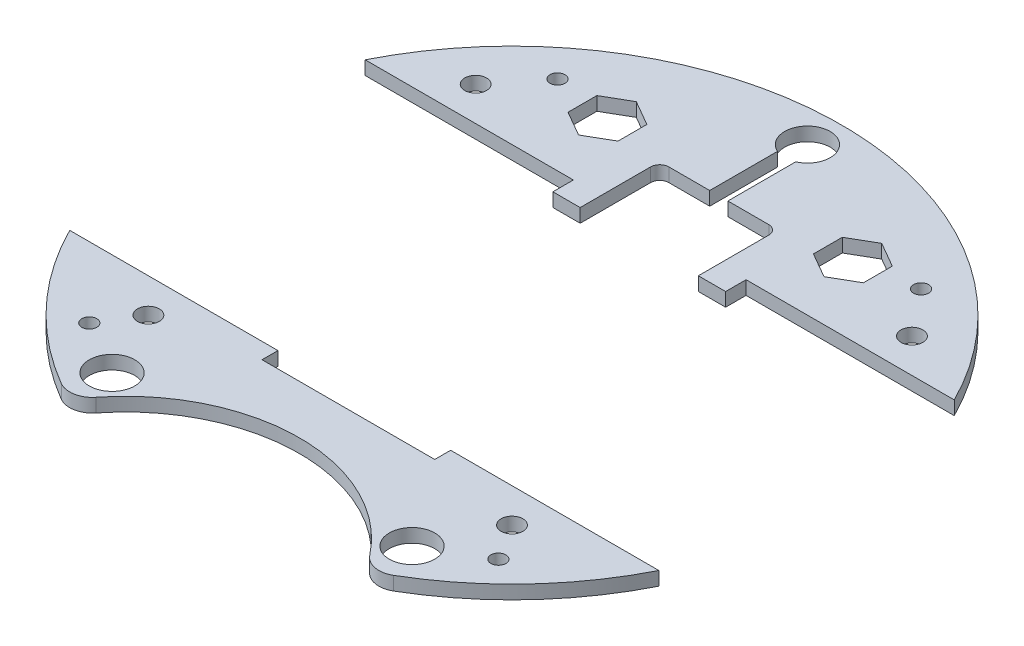
SolidWorks part; units mm, degrees
material "Acrylic (Medium-high impact)"
ref_plane "Front Plane" through (0, 0, 0) normal (0, 0, 1) x (1, 0, 0)
ref_plane "Top Plane" through (0, 0, 0) normal (0, 1, 0) x (1, 0, 0)
ref_plane "Right Plane" through (0, 0, 0) normal (1, 0, 0) x (0, 0, -1)
sketch "Sketch1" plane through (0, 0, 0) normal (0, 1, 0) x (1, 0, 0)
  line L0 (0, -85) -> (-32.4891, -64.8129) construction
  line L1 (0, -85) -> (0, 0) construction
  arc A0 (36.5434, -62.6165) -> (-36.5434, -62.6165) centre (0, 0) ccw
  arc A1 (30.0898, -61.3851) -> (-30.0898, -61.3851) centre (0, -85) ccw
  arc A2 (36.5434, -62.6165) -> (30.0898, -61.3851) centre (34.0231, -58.2982) cw
  arc A3 (-30.0898, -61.3851) -> (-36.5434, -62.6165) centre (-34.0231, -58.2982) cw
  dimension "D1" = 145
  dimension "D2" = 76.5
  dimension "D4" = 5
  dimension "D3" = 85
extrude "Boss-Extrude1" add sketch "Sketch1" along normal blind 3
sketch "solenoid placement" plane through (0, 3, 0) normal (0, 1, 0) x (1, 0, 0)
  line L4 (-19, -36) -> (19, -36)
  line L5 (-19, 28) -> (-19, -36)
  line L6 (19, 28) -> (-19, 28)
  line L7 (19, -36) -> (19, 28)
  line L8 (-19, -36) -> (19, -36)
  line L9 (-19, 28) -> (-19, -36)
  line L10 (19, 28) -> (-19, 28)
  line L11 (19, -36) -> (19, 28)
  dimension "D1" = 0
extrude "Cut-Extrude1" cut sketch "solenoid placement" against normal through all
sketch "Sketch5" plane through (0, 3, 0) normal (0, 1, 0) x (1, 0, 0)
  line L12 (-21.5, 51.1754) -> (-27, 54.3509)
  line L13 (-27, 54.3509) -> (-32.5, 51.1754)
  line L14 (-32.5, 51.1754) -> (-32.5, 44.8246)
  line L15 (-32.5, 44.8246) -> (-27, 41.6491)
  line L16 (-27, 41.6491) -> (-21.5, 44.8246)
  line L17 (-21.5, 44.8246) -> (-21.5, 51.1754)
  line L18 (-21.5, 51.1754) -> (-27, 54.3509)
  line L19 (-27, 54.3509) -> (-32.5, 51.1754)
  line L20 (-32.5, 51.1754) -> (-32.5, 44.8246)
  line L21 (-32.5, 44.8246) -> (-27, 41.6491)
  line L22 (-27, 41.6491) -> (-21.5, 44.8246)
  line L23 (-21.5, 44.8246) -> (-21.5, 51.1754)
  line L24 (21.5, 51.1754) -> (21.5, 44.8246)
  line L25 (21.5, 44.8246) -> (27, 41.6491)
  line L26 (27, 41.6491) -> (32.5, 44.8246)
  line L27 (32.5, 44.8246) -> (32.5, 51.1754)
  line L28 (32.5, 51.1754) -> (27, 54.3509)
  line L29 (27, 54.3509) -> (21.5, 51.1754)
  line L42 (21.5, 51.1754) -> (21.5, 44.8246)
  line L43 (21.5, 44.8246) -> (27, 41.6491)
  line L44 (27, 41.6491) -> (32.5, 44.8246)
  line L45 (32.5, 44.8246) -> (32.5, 51.1754)
  line L46 (32.5, 51.1754) -> (27, 54.3509)
  line L47 (27, 54.3509) -> (21.5, 51.1754)
  dimension "D1" = 0
  dimension "D2" = 0
extrude "Cut-Extrude5" cut sketch "Sketch5" against normal through all
sketch "Sketch6" plane through (0, 3, 0) normal (0, 1, 0) x (1, 0, 0)
  circle A0 centre (48, 40) radius 2.4
  circle A1 centre (40, -40) radius 2.4
  circle A2 centre (40, -40) radius 2.4 construction
  circle A3 centre (-40, -40) radius 2.4
  circle A4 centre (-40, -40) radius 2.4 construction
  circle A5 centre (48, 40) radius 2.4
  circle A6 centre (48, 40) radius 2.4 construction
  circle A7 centre (-48, 40) radius 2.4
  circle A8 centre (-48, 40) radius 2.4 construction
  circle A9 centre (-48, 40) radius 2.4
  circle A10 centre (40, -40) radius 2.4
  circle A11 centre (-40, -40) radius 2.4
  dimension "D5" = 4.8
extrude "Cut-Extrude6" cut sketch "Sketch6" against normal through all
sketch "Sketch3" plane through (0, 3, 0) normal (0, 1, 0) x (1, 0, 0)
  line L0 (-19, 28) -> (-19, 32.5)
  line L1 (72.5, -32.5) -> (-72.5, -32.5)
  line L2 (72.5, -32.5) -> (72.5, 32.5)
  line L3 (72.5, 32.5) -> (19, 32.5)
  line L4 (-72.5, -32.5) -> (-72.5, 32.5)
  line L5 (72.5, -32.5) -> (-72.5, 32.5) construction
  line L6 (72.5, 32.5) -> (-72.5, -32.5) construction
  line L7 (-19, 28) -> (19, 28)
  line L8 (19, 28) -> (19, 32.5)
  line L9 (-19, 32.5) -> (-72.5, 32.5)
  line L10 (-19, 28) -> (-19, -36) construction
  arc A0 (36.5434, -62.6165) -> (-36.5434, -62.6165) centre (0, 0) ccw construction
  point P0 (0, 0)
  dimension "D1" = 65
extrude "Cut-Extrude3" cut sketch "Sketch3" against normal through all
sketch "Sketch7" plane through (0, 3, 0) normal (0, 1, 0) x (1, 0, 0)
  line L8 (13, 28) -> (13, 43.5)
  line L9 (-13, 28) -> (13, 28)
  line L10 (-13, 43.5) -> (-13, 28)
  line L11 (11, 45.5) -> (-11, 45.5)
  line L28 (13, 28) -> (13, 43.5)
  line L29 (-13, 28) -> (13, 28)
  line L30 (-13, 43.5) -> (-13, 28)
  line L31 (11, 45.5) -> (-11, 45.5)
  arc A4 (-11, 45.5) -> (-13, 43.5) centre (-11, 43.5) ccw
  arc A5 (13, 43.5) -> (11, 45.5) centre (11, 43.5) ccw
  arc A14 (-11, 45.5) -> (-13, 43.5) centre (-11, 43.5) ccw
  arc A15 (13, 43.5) -> (11, 45.5) centre (11, 43.5) ccw
  dimension "D1" = 0
extrude "Cut-Extrude7" cut sketch "Sketch7" against normal through all
sketch "Sketch8" plane through (0, 3, 0) normal (0, 1, 0) x (1, 0, 0)
  line L0 (0, 0) -> (0, -21.9152) construction
  circle A1 centre (33, -55) radius 5
  circle A4 centre (-33, -55) radius 5
  dimension "D3" = 10
  dimension "D1" = 33
  dimension "D2" = 55
extrude "Cut-Extrude8" cut sketch "Sketch8" against normal through all
sketch "Sketch9" plane through (0, 3, 0) normal (0, 1, 0) x (1, 0, 0)
  line L0 (0, 0) -> (0, 65) construction
  line L1 (2, 0) -> (2, 60.4174)
  line L2 (-2, 0) -> (-2, 60.4174)
  line L3 (2, 0) -> (2, 65) construction
  line L4 (-2, 0) -> (-2, 65) construction
  arc A0 (2, 60.4174) -> (-2, 60.4174) centre (0, 65) ccw
  arc A1 (2, 0) -> (-2, 0) centre (0, 0) cw
  dimension "D1" = 10
  dimension "D2" = 65
  dimension "D3" = 2
  dimension "D4" = 2
extrude "Cut-Extrude9" cut sketch "Sketch9" against normal through all
sketch "Sketch10" plane through (0, 3, 0) normal (0, 1, 0) x (1, 0, 0)
  line L0 (0, 0) -> (0, -25.927) construction
  circle A0 centre (45, -48) radius 1.65
  circle A1 centre (-45, -48) radius 1.65
  circle A2 centre (40, 50) radius 1.65
  circle A3 centre (-40, 50) radius 1.65
  dimension "D3" = 3.3
  dimension "D1" = 45
  dimension "D2" = 48
  dimension "D4" = 40
  dimension "D5" = 50
extrude "Cut-Extrude10" cut sketch "Sketch10" against normal blind 10
equation "\"smallPulleyTeeth\"= 30"
equation "\"largePulleyTeeth\"= 30"
equation "\"eighthThick\"= 3.0mm"
equation "\"sixteenthThick\" = 1.7mm"
equation "\"quarterThick\"=6.0mm"
equation "\"OD\" = 145mm"
equation "\"puckAngle\" = 60.5deg"
equation "\"D1@Sketch1\"=\"OD\""
equation "\"puckDiam\" = 76.5mm"
equation "\"D2@Sketch1\"=\"puckDiam\""
equation "\"D1@Boss-Extrude1\"=\"eighthThick\""
equation "\"axlePress\" = 5.9mm"
equation "\"press\" = 0.2mm"
equation "\"wheelClear\" = 0.3mm"
equation "\"10-32clear\" = 4.8mm"
equation "\"6-32clear\" = 3.3mm"
equation "\"8-32clear\" = 4.0mm"
equation "\"wheelHeight\" = 22mm"
equation "\"wheelWell\" = 65mm"
equation "\"D1@Sketch3\"=\"wheelWell\""
equation "\"puckDist\" = 85mm"
equation "\"scoopFillet\" = 5mm"
equation "\"4-40clear\" = 3.0mm"
equation "\"D3@Sketch1\"=\"puckDist\""
equation "\"D4@Sketch1\"=\"scoopFillet\""
equation "\"10-32tap\" = 4.45mm"
equation "\"D5@Sketch6\"=\"10-32clear\""
equation "\"D3@Sketch10\"=\"6-32clear\""
